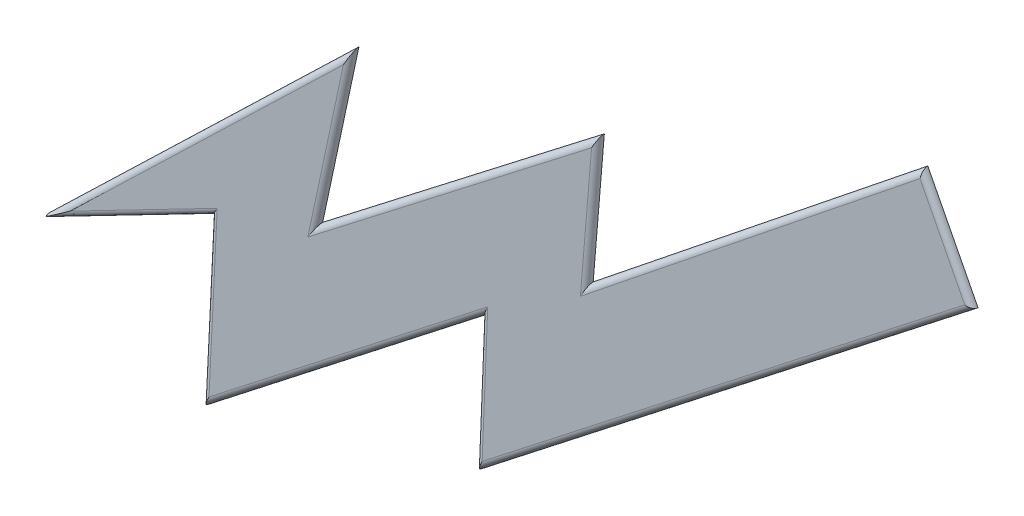
SolidWorks part; units mm, degrees
ref_plane "Front Plane" through (0, 0, 0) normal (0, 0, 1) x (1, 0, 0)
ref_plane "Top Plane" through (0, 0, 0) normal (0, 1, 0) x (1, 0, 0)
ref_plane "Right Plane" through (0, 0, 0) normal (1, 0, 0) x (0, 0, -1)
sketch "Model" plane through (0, 0, 0) normal (0, 0, 1) x (1, 0, 0)
  line L0 (80.7682, 56.3471) -> (38.3361, 23.2118)
  line L1 (38.3361, 23.2118) -> (38.8129, 34.8926)
  line L2 (38.8129, 34.8926) -> (14.9744, 16.2989)
  line L3 (14.9744, 16.2989) -> (15.6896, 30.8404)
  line L4 (15.6896, 30.8404) -> (1.3867, 23.4506)
  line L5 (1.3867, 23.4506) -> (1.3867, 23.6888)
  line L6 (1.3867, 23.6888) -> (27.8472, 49.1954)
  line L7 (27.8472, 49.1954) -> (24.7483, 34.6544)
  line L8 (24.7483, 34.6544) -> (48.8249, 53.2482)
  line L9 (48.8249, 53.2482) -> (47.8717, 41.8056)
  line L10 (47.8717, 41.8056) -> (76.4774, 64.6907)
  line L11 (76.4774, 64.6907) -> (80.7682, 56.3471)
extrude "Boss-Extrude1" add sketch "Model" along normal blind 0.5
fillet "Fillet1" radius 0.5 11 edges at (59.5521, 39.7795, 0.5) (38.5745, 29.0522, 0.5) (26.8936, 25.5957, 0.5) (15.332, 23.5696, 0.5) (8.5382, 27.1455, 0.5) (14.617, 36.4421, 0.5) (26.2978, 41.9249, 0.5) (36.7866, 43.9513, 0.5) (48.3483, 47.5269, 0.5) (62.1745, 53.2482, 0.5) (78.6228, 60.5189, 0.5)
